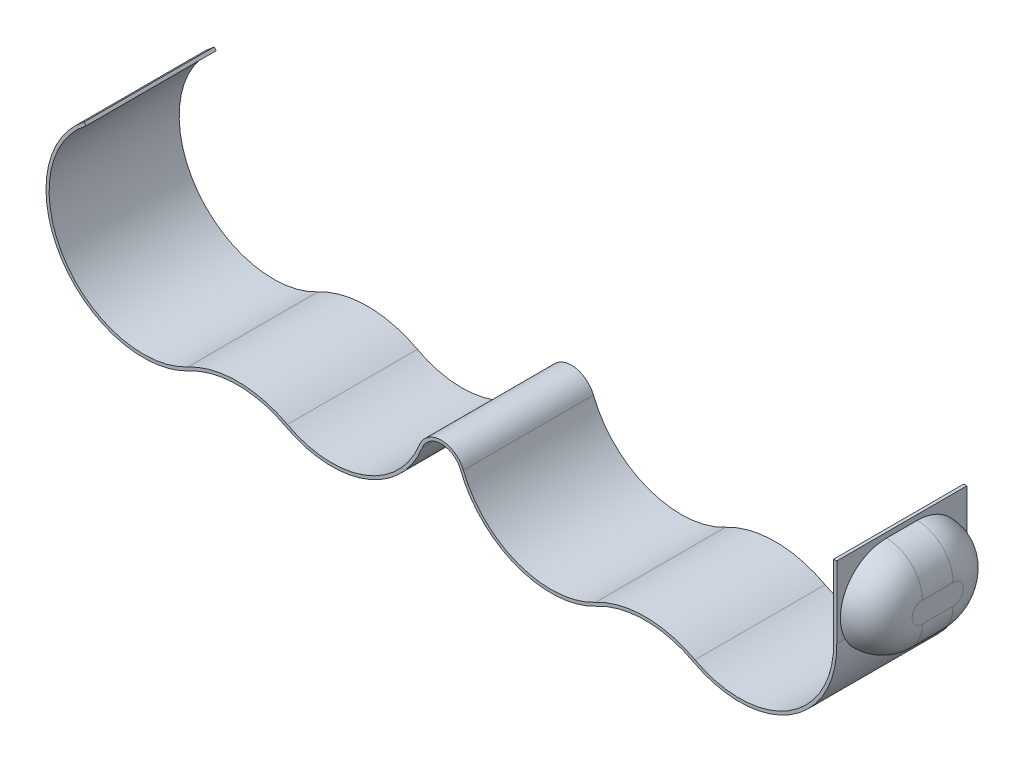
SolidWorks part; units mm, degrees
ref_plane "Front Plane" through (0, 0, 0) normal (0, 0, 1) x (1, 0, 0)
ref_plane "Top Plane" through (0, 0, 0) normal (0, 1, 0) x (1, 0, 0)
ref_plane "Right Plane" through (0, 0, 0) normal (1, 0, 0) x (0, 0, -1)
sketch "Battery Holder Outline" plane through (0, 0, 0) normal (0, 0, 1) x (1, 0, 0)
  line L0 (1.8682, 8) -> (-1.8682, 8) construction
  line L1 (-37.9318, 8) -> (-42.3, 8) construction
  line L2 (-42.3, 8) -> (-42.3, 0) construction
  line L3 (37.9318, 8) -> (42.3, 8) construction
  line L4 (42.3, 8) -> (42.3, 0) construction
  line L5 (42.3, 0) -> (-42.3, 0) construction
  arc A0 (-1.8682, 8) -> (-15.1821, 3.1238) centre (-10.7, 11.5) cw construction
  arc A1 (-24.6179, 3.1238) -> (-37.9318, 8) centre (-29.1, 11.5) cw construction
  arc A2 (24.6179, 3.1238) -> (37.9318, 8) centre (29.1, 11.5) ccw construction
  arc A3 (1.8682, 8) -> (15.1821, 3.1238) centre (10.7, 11.5) ccw construction
  arc A4 (24.6179, 3.1238) -> (15.1821, 3.1238) centre (19.9, -5.6933) ccw construction
  arc A5 (-15.1821, 3.1238) -> (-24.6179, 3.1238) centre (-19.9, -5.6933) ccw construction
  point P15 (0, 0)
  point P19 (0, 0)
  point P20 (0, 0)
  point P21 (0, 0)
  dimension "D1" = 9.5
  dimension "D2" = 10
  dimension "D3" = 84.6
  dimension "D4" = 8
  dimension "D5" = 3.7365
  dimension "D6" = 11.5
  dimension "D7" = 4.3682
sketch "Sketch2" plane through (0, 0, 0) normal (0, 0, 1) x (1, 0, 0)
  line L3 (-34.8747, 19.0434) -> (-34.6924, 18.8052)
  line L7 (38.5984, 11.6746) -> (38.5984, 18.6691)
  line L8 (38.5984, 18.6691) -> (38.2984, 18.6691)
  line L9 (38.2984, 18.6691) -> (38.2984, 11.6691)
  arc A0 (-15.1821, 3.1238) -> (-1.8682, 8) centre (-10.7, 11.5) ccw construction
  arc A1 (-15.1821, 3.1238) -> (-24.6179, 3.1238) centre (-19.9, -5.6933) ccw construction
  arc A2 (-37.9318, 8) -> (-24.6179, 3.1238) centre (-29.1, 11.5) ccw construction
  arc A3 (-15.1821, 3.1238) -> (-1.8682, 8) centre (-10.7, 11.5) ccw
  arc A4 (-15.1821, 3.1238) -> (-24.6179, 3.1238) centre (-19.9, -5.6933) ccw
  arc A5 (-37.9318, 8) -> (-24.6179, 3.1238) centre (-29.1, 11.5) ccw
  arc A13 (24.6179, 3.1238) -> (15.1821, 3.1238) centre (19.9, -5.6933) ccw construction
  arc A14 (1.8682, 8) -> (15.1821, 3.1238) centre (10.7, 11.5) ccw construction
  arc A15 (24.6179, 3.1238) -> (37.9318, 8) centre (29.1, 11.5) ccw construction
  arc A16 (24.6179, 3.1238) -> (38.5984, 11.6746) centre (29.1, 11.5) ccw
  arc A17 (24.6179, 3.1238) -> (15.1821, 3.1238) centre (19.9, -5.6933) ccw
  arc A18 (1.8682, 8) -> (15.1821, 3.1238) centre (10.7, 11.5) ccw
  arc A19 (-1.8682, 8) -> (1.8682, 8) centre (0, 7.2596) cw
  arc A21 (-37.9318, 8) -> (-34.8747, 19.0434) centre (-29.1, 11.5) cw
  arc A22 (-37.6529, 8.1105) -> (-34.6924, 18.8052) centre (-29.1, 11.5) cw
  arc A23 (-37.6529, 8.1105) -> (-24.7595, 3.3883) centre (-29.1, 11.5) ccw
  arc A24 (-15.0405, 3.3883) -> (-24.7595, 3.3883) centre (-19.9, -5.6933) ccw
  arc A25 (-15.0405, 3.3883) -> (-2.1471, 8.1105) centre (-10.7, 11.5) ccw
  arc A26 (-2.1471, 8.1105) -> (2.1471, 8.1105) centre (0, 7.2596) cw
  arc A27 (2.1471, 8.1105) -> (15.0405, 3.3883) centre (10.7, 11.5) ccw
  arc A28 (24.7595, 3.3883) -> (15.0405, 3.3883) centre (19.9, -5.6933) ccw
  arc A29 (24.7595, 3.3883) -> (38.2984, 11.6691) centre (29.1, 11.5) ccw
  arc A31 (38.5984, 11.6746) -> (37.4623, 16.008) centre (29.1, 11.5) ccw construction
  arc A32 (38.2984, 11.6691) -> (37.1982, 15.8656) centre (29.1, 11.5) ccw construction
  point P6 (37.9237, 15.0203)
  point P8 (38.5984, 18.8052)
  dimension "D1" = 0.3
  dimension "D4" = 7
  dimension "D2" = 19.1406
  dimension "D3" = 12.3
extrude "Boss-Extrude1" add sketch "Sketch2" along normal mid plane 12.7
ref_plane "Plane1" through (37.9237, 15.0203, 0) normal (0.9288, 0.3706, 0) x (0, 0, -1)
ref_plane "Plane2" through (42.5677, 16.8731, 0) normal (0.9288, 0.3706, 0) x (0, 0, -1)
sketch "Sketch6" plane through (38.5984, 16.1106, 0) normal (1, 0, 0) x (0, 0, -1)
  line L0 (-1.5, -2.4415) -> (1.5, -2.4415) construction
  line L1 (-1.5, 2.0585) -> (1.5, 2.0585)
  line L2 (-1.5, -6.9415) -> (1.5, -6.9415)
  line L3 (-6.35, 2.5585) -> (6.35, 2.5585) construction
  arc A0 (-1.5, 2.0585) -> (-1.5, -6.9415) centre (-1.5, -2.4415) ccw
  arc A1 (1.5, -6.9415) -> (1.5, 2.0585) centre (1.5, -2.4415) ccw
  point P2 (0, -2.4415)
  point P7 (0, 0)
  point P8 (0.264, -2.5619)
  point P11 (0, 0)
  point P12 (0, 2.5585)
  point P14 (6, -2.4415)
  point P15 (-6, -2.4415)
  dimension "D1" = 12
  dimension "D3" = 0.5
  dimension "D2" = 9
extrude "Boss-Extrude3" add sketch "Sketch6" against normal up to next (0.2999 mm away) and the other way blind 3.51
sketch "Sketch5" plane through (0, 0, 6.35) normal (0, 0, 1) x (1, 0, 0)
  line L2 (36.9572, 21.8694) -> (47.6324, 21.8694)
  line L3 (47.6324, 21.8694) -> (47.6324, 11.5)
  line L4 (47.6324, 11.5) -> (42.11, 11.5)
  line L5 (38.5984, 18.1691) -> (42.1084, 18.1691) construction
  arc A0 (24.7595, 3.3883) -> (38.2984, 11.6691) centre (29.1, 11.5) ccw construction
  arc A1 (36.9572, 21.8694) -> (42.11, 11.5) centre (29.1, 11.5) cw
  point P0 (29.1, 11.5)
  dimension "D1" = 13.01
  dimension "D3" = 12
  dimension "D2" = 5.5224
extrude "Cut-Extrude1" [suppressed] cut sketch "Sketch5" against normal through all
fillet "Fillet1" [suppressed] radius 3.5 type face fillet
fillet "Fillet2" radius 3.5 4 edges at (42.1084, 18.1691, 0) (42.1084, 13.6691, -6) (42.1084, 9.1691, 0) (42.1084, 13.6691, 6)
